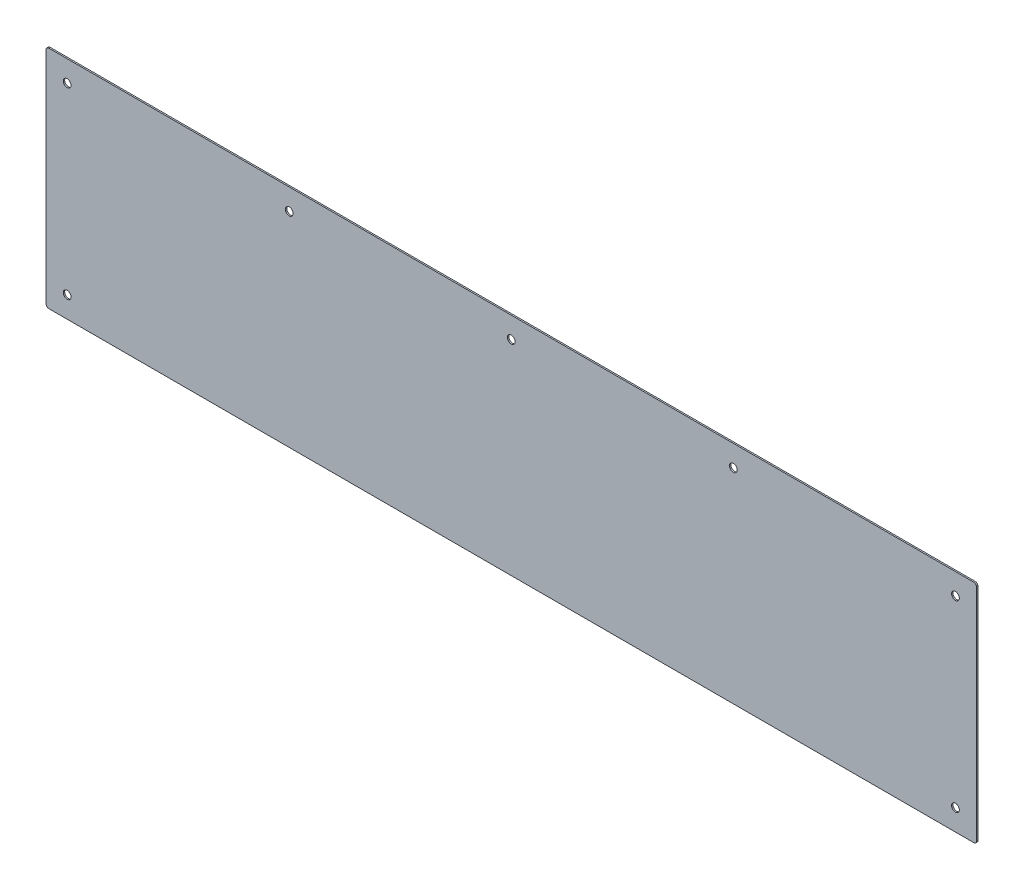
SolidWorks part; units mm, degrees
material "3.3547 (EN-AW 5083)"
ref_plane "Front Plane" through (0, 0, 0) normal (0, 0, 1) x (1, 0, 0)
ref_plane "Top Plane" through (0, 0, 0) normal (0, 1, 0) x (1, 0, 0)
ref_plane "Right Plane" through (0, 0, 0) normal (1, 0, 0) x (0, 0, -1)
sketch "Sketch1" plane through (0, 0, 0) normal (0, 0, 1) x (1, 0, 0)
  line L1 (330, -80) -> (-330, -80)
  line L2 (330, -80) -> (330, 80)
  line L3 (330, 80) -> (-330, 80)
  line L4 (-330, -80) -> (-330, 80)
  line L5 (330, -80) -> (-330, 80) construction
  line L6 (330, 80) -> (-330, -80) construction
  point P0 (0, 0)
  dimension "D1" = 660
  dimension "D2" = 160
base flange "Base-Flange1" sketch "Sketch1" thickness 1 reverse thickness direction no parameters "D1"=0.7366
hole_wizard "M5 Clearance Hole2" positions "Sketch22" profile "Sketch23" hole size "M5" standard "DIN" end condition up to next
sketch "Sketch22" plane through (0, 0, 0) normal (0, 0, 1) x (1, 0, 0)
  line L0 (0, 0) -> (0, 80) construction
  line L1 (330, 80) -> (-330, 80) construction
  line L2 (-330, 0) -> (0, 0) construction
  line L6 (-330, 80) -> (-330, -80) construction
  line L7 (-315, 65) -> (0, 65) construction
  point P17 (-315, 65)
  point P20 (-315, -65)
  point P21 (315, -65)
  point P23 (315, 65)
  point P34 (-157.5, 65)
  point P38 (157.5, 65)
  point P45 (0, 65)
  dimension "D1" = 15
  dimension "D2" = 15
sketch "Sketch23" plane through (0, 65, 0) normal (1, 0, 0) x (0, -1, 0)
  line L0 (0, 0) -> (0, 1)
  line L1 (0, 1) -> (2.75, 1)
  line L2 (2.75, 1) -> (2.75, 0)
  line L5 (2.75, 0) -> (0, 0)
  line L11 (0, -6.35) -> (0, 107.95) construction
  dimension "Thru Hole Dia." = 5.5
  dimension "Thru Hole Depth" = 1
fillet "Fillet1" radius 2 4 edges at (330, -80, -0.5) (330, 80, -0.5) (-330, -80, -0.5) (-330, 80, -0.5)
sketch "Bend-Lines1" [suppressed] plane through (0, 0, 0) normal (0, 1, 0) x (1, 0, 0)
sketch "Bounding-Box1" [suppressed] plane through (0, 0, 0) normal (0, 1, 0) x (1, 0, 0)
sheet metal parameters "Sheet-Metal1" thickness 1 parameters "D1"=0.7366
flat pattern "Flat-Pattern1" [suppressed]
sketch "Bend-Lines2" plane through (0, 0, 0) normal (0, 1, 0) x (1, 0, 0)
sketch3d "Bounding-Box2" [suppressed]
  line L0 (-330, -82.5, 0) -> (330, -82.5, 0) construction
  line L1 (-330, 82.5, 0) -> (330, 82.5, 0) construction
  line L2 (-330, -82.5, 0) -> (-330, 82.5, 0) construction
  line L3 (330, -82.5, 0) -> (330, 82.5, 0) construction
sheet metal parameters "Sheet-Metal9" thickness 1 parameters "D1"=0.7366
flat pattern "Flat-Pattern1"
sketch "Bend-Lines2" plane through (0, 0, 0) normal (0, 0, 1) x (1, 0, 0)
sketch3d "Bounding-Box2" [suppressed]
  line L0 (-329.9999, 80.0004, 0) -> (330, 80, 0) construction
  line L1 (-330, -79.9996, 0) -> (329.9999, -80, 0) construction
  line L2 (-329.9999, 80.0004, 0) -> (-330, -79.9996, 0) construction
  line L3 (330, 80, 0) -> (329.9999, -80, 0) construction
